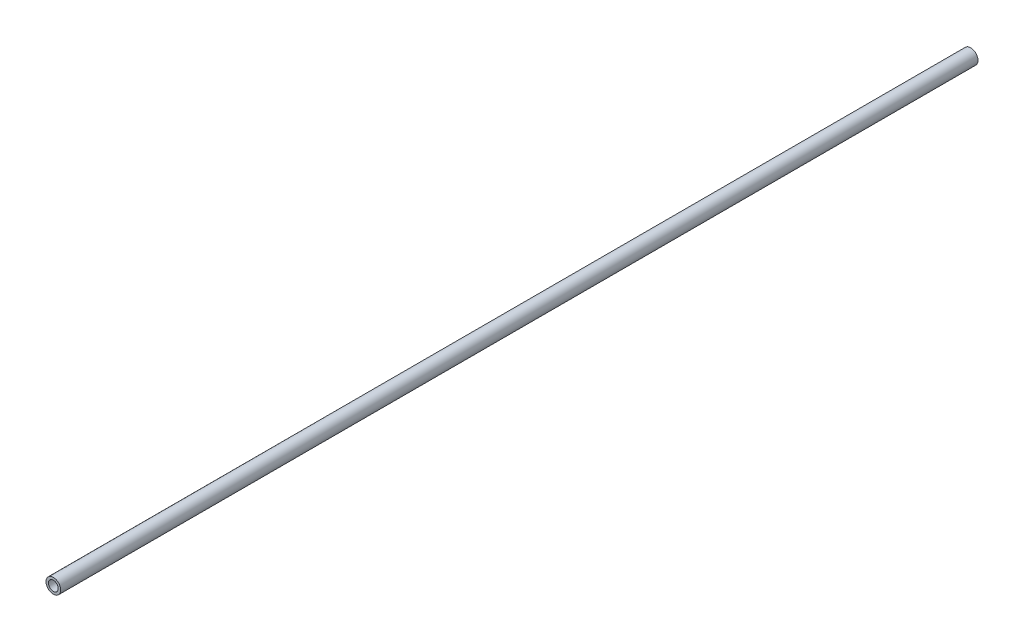
SolidWorks part; units mm, degrees
material "ABS PC"
ref_plane "Alzado" through (0, 0, 0) normal (1, 0, 0) x (0, 1, 0)
ref_plane "Planta" through (0, 0, 0) normal (0, 0, 1) x (0, 1, 0)
ref_plane "Vista lateral" through (0, 0, 0) normal (0, 1, 0) x (-1, 0, 0)
sketch "Croquis2" plane through (0, 0, 0) normal (0, 0, 1) x (0, 1, 0)
  circle A0 centre (0, 0) radius 4.8
  circle A1 centre (0, 0) radius 3.2
  dimension "D1" = 1.6
  dimension "D2" = 6.4
extrude "Saliente-Extruir1" add sketch "Croquis2" along normal blind 600
